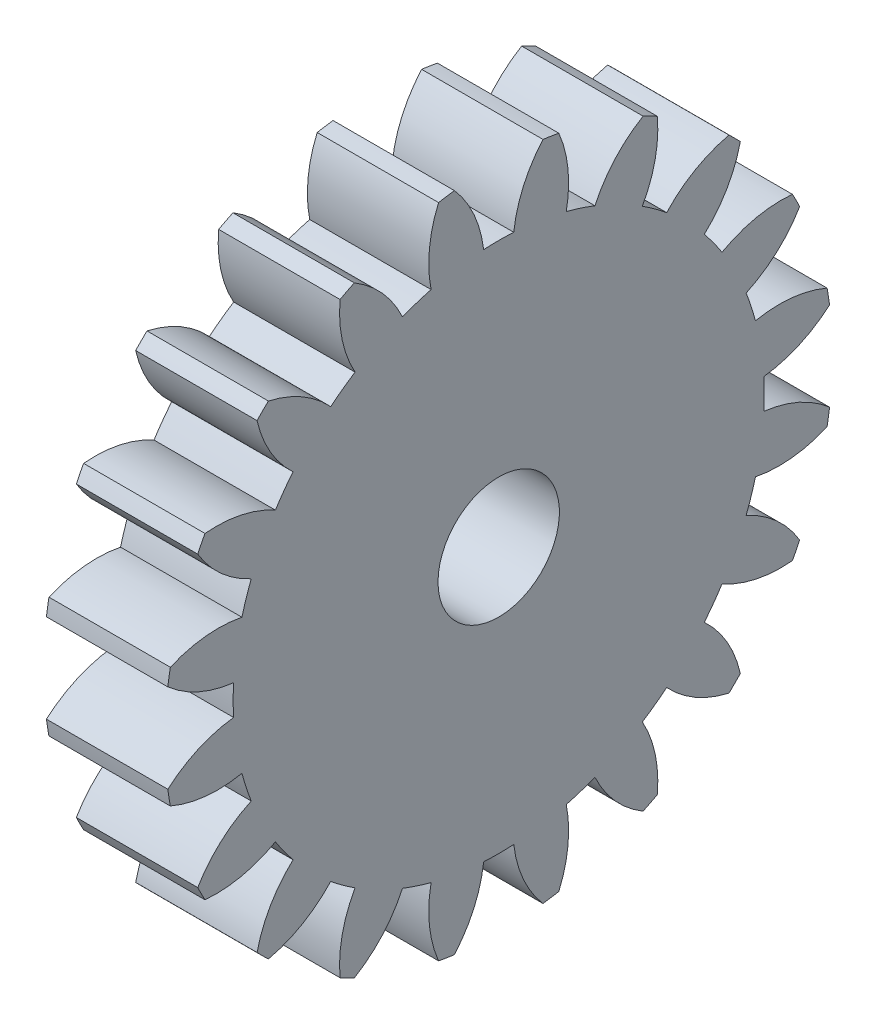
SolidWorks part; units mm, degrees
ref_plane "Plane1" through (0, 0, 0) normal (0, 0, 1) x (1, 0, 0)
ref_plane "Plane2" through (0, 0, 0) normal (0, 1, 0) x (1, 0, 0)
ref_plane "Plane3" through (0, 0, 0) normal (1, 0, 0) x (0, 0, -1)
sketch "HoldingSke" plane through (0, 0, 0) normal (0, 1, 0) x (1, 0, 0)
  line L0 (0, 0) -> (0.6265, -0.228)
  line L1 (-15, 0) -> (100, 0) construction
  line L2 (0, 0) -> (-2.1039, 2.3779)
  line L3 (0, 0) -> (-11.863, 4.5341)
  line L4 (0, 0) -> (8.1152, 2.9537)
  line L5 (0, 0) -> (-46.8476, -17.4728)
  line L6 (0, 0) -> (-4.9738, -3.3558)
  line L7 (-2.1039, 2.3779) -> (8.6586, 51.2059)
  line L8 (-76.2, 54.61) -> (-75.2, 54.61)
  line L9 (-71.009, 38.7566) -> (-53.1078, 45.2721)
  line L10 (-76.2, 71.12) -> (104.1128, 71.12)
  line L11 (0, 0) -> (-6, 0)
  line L12 (-76.2, 101.6) -> (-76.147, 101.6)
  line L13 (24.9733, 27.94) -> (52.9518, 28.4284)
  line L14 (24.9733, 27.94) -> (24.9743, 27.94)
  line L15 (24.9733, 27.94) -> (100.4006, 29.5858)
  line L16 (-63.627, -1.5) -> (-12.827, -1.5)
  circle A0 centre (0, 0) radius 3
  circle A1 centre (0, 0) radius 13.124
  circle A2 centre (0, 0) radius 37.5
  circle A3 centre (0, 0) radius 3
  dimension "Num_teeth" = 20
  dimension "Pitch_radius" = 180.3128
  dimension "Width" = 6
  dimension "Thickness" = 6
sketch "BasProSke" plane through (0, 0, 0) normal (0, 1, 0) x (1, 0, 0)
  line L0 (-10, 0) -> (60, 0) construction
  line L1 (0, 0) -> (0, 16.5)
  line L2 (0, 0) -> (6, 0)
  line L3 (6, 0) -> (6, 16.5)
  line L4 (6, 16.5) -> (0, 16.5)
  dimension "Thickness" = 6
  dimension "Diameter" = 33
revolve "Base-Revolve" add sketch "BasProSke" angle 360 about L0
sketch "TooCutSke" plane through (0, 0, 0) normal (1, 0, 0) x (0, 0, -1)
  line L1 (0, 0) -> (0, 107) construction
  line L2 (0, 0) -> (-1.2696, 14.9462) construction
  line L3 (0, 0) -> (-4.6808, 29.5532) construction
  line L4 (-1.2696, 14.9462) -> (-2.3404, 14.7766) construction
  arc A0 (0.7438, 13.1029) -> (-0.7438, 13.1029) centre (0, 0) ccw
  arc A1 (2.21, 16.377) -> (-2.21, 16.377) centre (0, 0) ccw
  circle A2 centre (0, 0) radius 15 construction
  circle A3 centre (0, 0) radius 14.0954 construction
  arc A4 (-0.7438, 13.1029) -> (-2.21, 16.377) centre (-6.7025, 12.3999) ccw
  arc A5 (2.21, 16.377) -> (0.7438, 13.1029) centre (6.7025, 12.3999) ccw
extrude "ToothCut" cut sketch "TooCutSke" along normal through all
fillet "Breaks" [suppressed] radius 0.03 tangent propagation no
fillet "RootFillets" [suppressed] radius 0.376
pattern_circular "TeethCuts" count 20 every 18 about axis through (-10, 0, 0) along (1, 0, 0) of "ToothCut", "RootFillets", "Breaks"
sketch "HubNeaOneSke" plane through (0, 0, 0) normal (-1, 0, 0) x (0, 0, 1)
  circle A0 centre (0, 0) radius 13.124
  dimension "Diameter" = 26.248
extrude "HubNearOne" [suppressed] add sketch "HubNeaOneSke" along normal blind 44.0001
sketch "HubNeaBotSke" plane through (0, 0, 0) normal (-1, 0, 0) x (0, 0, 1)
  circle A0 centre (0, 0) radius 13.124
  dimension "Diameter" = 26.248
extrude "HubNearBoth" [suppressed] add sketch "HubNeaBotSke" along normal blind 22
ref_plane "FarPln" through (6, 0, 0) normal (1, 0, 0) x (0, 0, -1)
sketch "HubFarSke" plane through (6, 0, 0) normal (1, 0, 0) x (0, 0, -1)
  circle A0 centre (0, 0) radius 13.124
  dimension "Diameter" = 26.248
extrude "HubFar" [suppressed] add sketch "HubFarSke" along normal blind 22
sketch "BorSke" plane through (0, 0, 0) normal (1, 0, 0) x (0, 0, -1)
  circle A0 centre (0, 0) radius 3
  dimension "Diameter" = 6
extrude "Bore" cut sketch "BorSke" along normal mid plane 100.0001
sketch "KeySke" plane through (0, 0, 0) normal (1, 0, 0) x (0, 0, -1)
  line L0 (-1, 0) -> (-1, 4)
  line L1 (-1, 4) -> (1, 4)
  line L2 (1, 4) -> (1, 0)
  line L3 (0, 0) -> (0, 34) construction
  line L4 (-1, 0) -> (1, 0)
  dimension "Width" = 2
extrude "Keyway" [suppressed] cut sketch "KeySke" along normal mid plane 100.0001
pattern_circular "Keyway2" [suppressed] count 2 every 90 about axis through (-10, 0, 0) along (1, 0, 0) reverse direction yes
equation "' \"Module@HoldingSke\" = 6.35"
equation "' \"Num_teeth@HoldingSke\" = 12"
equation "' \"Ap@HoldingSke\" =  20"
equation "' \"Ap@HoldingSke\" = 20"
equation "' \"Width@HoldingSke\" = 0.5 * 25.4"
equation "' \"Hub_dia@HoldingSke\"= 1 * 25.4"
equation "' \"Hub_dia@HoldingSke\" = 1 * 25.4"
equation "' \"Overall_len@HoldingSke\" = 1.0 * 25.4"
equation "' \"Bore@HoldingSke\" = 0.75 * 25.4"
equation "' \"T_dim@HoldingSke\" = 0.1 * 25.4"
equation "' \"Width@KeySke\" = 0.25 * 25.4"
equation "' \"Show_teeth@HoldingSke\" = 13"
equation "' \"Backlash@HoldingSke\" = 0.009 * 25.4"
equation "' \"Addendum_fac@HoldingSke\" = 1.0"
equation "' \"Dedendum_fac@HoldingSke\" = 1.25"
equation "' \"Dedendum_add@HoldingSke\" = 0.00005 * 25.4"
equation "' \"Clearance_fac@HoldingSke\" = 0.25"
equation "\"Pitch@HoldingSke\" = 1 / \"Module@HoldingSke\""
equation "\"Overcut_dia@TooCutSke\" = (\"Num_teeth@HoldingSke\" + 2 * \"Addendum_fac@HoldingSke\") / \"Pitch@HoldingSke\" + 0.002 * 25.4"
equation "\"Pitch_dia@TooCutSke\" = \"Num_teeth@HoldingSke\" / \"Pitch@HoldingSke\""
equation "\"Base_dia@TooCutSke\" = \"Num_teeth@HoldingSke\" / \"Pitch@HoldingSke\" * cos((\"Ap@HoldingSke\"  * 3.14159265 / 180))"
equation "\"Root_dia@TooCutSke\" = (\"Num_teeth@HoldingSke\" + 2) / \"Pitch@HoldingSke\" - 2 * (\"Addendum_fac@HoldingSke\" + \"Dedendum_fac@HoldingSke\") / \"Pitch@HoldingSke\" - \"Dedendum_add@HoldingSke\" * 2"
equation "\"Half_ang@TooCutSke\" = 180 / \"Num_teeth@HoldingSke\""
equation "\"Half_CT@TooCutSke\" = \"Num_teeth@HoldingSke\" / \"Pitch@HoldingSke\" * sin((3.14159265 / 2 / \"Num_teeth@HoldingSke\")) / 2 - 7 * \"Backlash@HoldingSke\" / 4"
equation "\"Flank_rad@TooCutSke\" = \"Num_teeth@HoldingSke\" / \"Pitch@HoldingSke\" / 5"
equation "\"Radius@RootFillets\" = \"Clearance_fac@HoldingSke\" / \"Pitch@HoldingSke\" + \"Dedendum_add@HoldingSke\""
equation "\"Break_rad@Breaks\" = 0.02 / \"Pitch@HoldingSke\""
equation "\"Thickness@HoldingSke\" = \"Width@HoldingSke\""
equation "\"OAL@HoldingSke\" = \"Thickness@HoldingSke\""
equation "\"MHD@HoldingSke\" = (\"Num_teeth@HoldingSke\" + 2) / \"Pitch@HoldingSke\" - 2 * (\"Addendum_fac@HoldingSke\" + \"Dedendum_fac@HoldingSke\")  / \"Pitch@HoldingSke\" - \"Dedendum_add@HoldingSke\" * 2"
equation "\"MBD@HoldingSke\" = (\"Num_teeth@HoldingSke\" + 2) / \"Pitch@HoldingSke\" - 2 * (\"Addendum_fac@HoldingSke\" + \"Dedendum_fac@HoldingSke\")  / \"Pitch@HoldingSke\" - \"Dedendum_add@HoldingSke\" * 2 - 0.002 * 25.4"
equation "\"MHD@HoldingSke\" = ((sgn( \"MHD@HoldingSke\" - \"Hub_dia@HoldingSke\" )-1)*( \"MHD@HoldingSke\" - \"Hub_dia@HoldingSke\" ))/-2+ \"Hub_dia@HoldingSke\""
equation "\"MBD@HoldingSke\" = ((sgn( \"MBD@HoldingSke\" - \"Bore@HoldingSke\" )-1)*( \"MBD@HoldingSke\" - \"Bore@HoldingSke\" ))/-2+ \"Bore@HoldingSke\""
equation "\"OAL@HoldingSke\" = ((sgn( \"OAL@HoldingSke\" - \"Overall_len@HoldingSke\" )+1)*( \"OAL@HoldingSke\" - \"Overall_len@HoldingSke\" ))/2 + \"Overall_len@HoldingSke\" + 0.000002 * 25.4"
equation "\"Num_teeth@TeethCuts\" = int( \"Show_teeth@HoldingSke\" ) + 1"
equation "\"Num_teeth@TeethCuts\" = ((sgn( \"Num_teeth@TeethCuts\" - \"Num_teeth@HoldingSke\" )-1)*( \"Num_teeth@TeethCuts\" - \"Num_teeth@HoldingSke\" ))/-2+ \"Num_teeth@HoldingSke\""
equation "\"Num_teeth@TeethCuts\" = ((sgn( \"Num_teeth@TeethCuts\" - 2.0)+1)*( \"Num_teeth@TeethCuts\" - 2.0))/2 +2.0"
equation "\"Angle@TeethCuts\" = 360.0 / \"Num_teeth@HoldingSke\""
equation "\"Diameter@BasProSke\" = (\"Num_teeth@HoldingSke\" + 2 * \"Addendum_fac@HoldingSke\") / \"Pitch@HoldingSke\""
equation "\"Thickness@BasProSke\"  = \"Thickness@HoldingSke\""
equation "' \"Fillet_rad@BasProSke\" =  \"Thickness@HoldingSke\" * 0.05"
equation "' \"Fillet_rad@BasProSke\" = \"Thickness@HoldingSke\" * 0.05"
equation "\"MHD@HoldingSke\" = ((sgn( \"MHD@HoldingSke\" - \"Root_dia@TooCutSke\" )-1)*( \"MHD@HoldingSke\" - \"Root_dia@TooCutSke\" ))/-2+ \"Root_dia@TooCutSke\""
equation "\"Diameter@HubNeaOneSke\" = \"MHD@HoldingSke\""
equation "\"Length@HubNearOne\" = \"OAL@HoldingSke\" - \"Thickness@BasProSke\""
equation "\"Diameter@HubNeaBotSke\" = \"MHD@HoldingSke\""
equation "\"Length@HubNearBoth\" = ( \"OAL@HoldingSke\" - \"Thickness@BasProSke\" ) / 2.0"
equation "\"Thickness@FarPln\" = \"Thickness@BasProSke\""
equation "\"Diameter@HubFarSke\" = \"MHD@HoldingSke\""
equation "\"Length@HubFar\" = ( \"OAL@HoldingSke\" - \"Thickness@BasProSke\" ) / 2.0"
equation "\"Diameter@BorSke\" = \"MBD@HoldingSke\""
equation "\"D1@Bore\" = \"OAL@HoldingSke\" * 2.0"
equation "\"D1@Keyway\" = \"OAL@HoldingSke\" * 2.0"
equation "\"Offset@KeySke\" = \"T_dim@HoldingSke\" + \"MBD@HoldingSke\" / 2.0"
